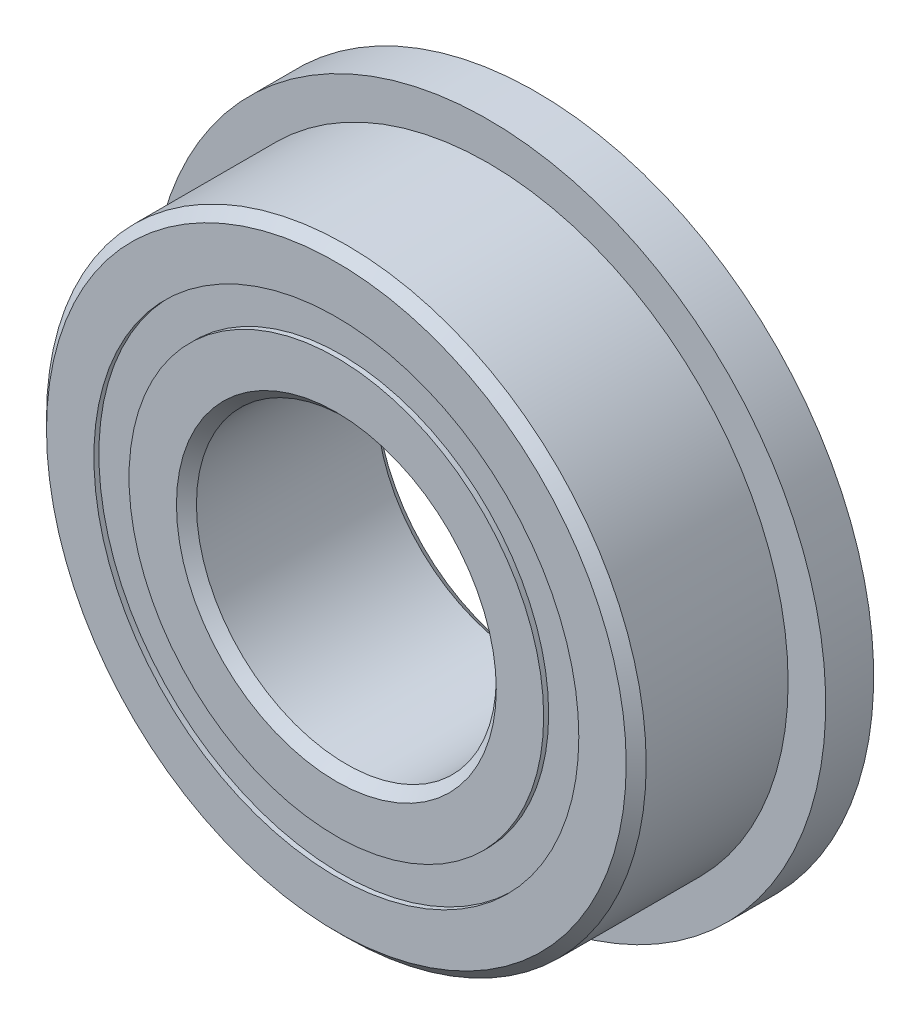
SolidWorks part; units mm, degrees
ref_plane "Front Plane" through (0, 0, 0) normal (0, 0, 1) x (1, 0, 0)
ref_plane "Top Plane" through (0, 0, 0) normal (0, 1, 0) x (1, 0, 0)
ref_plane "Right Plane" through (0, 0, 0) normal (1, 0, 0) x (0, 0, -1)
sketch "Sketch1" plane through (0, 0, 0) normal (1, 0, 0) x (0, 0, -1)
  line L0 (-1.5875, 0) -> (1.5875, 0) construction
  line L1 (0, 4.7625) -> (0, -4.7625) construction
  line L2 (1.5875, 4.7625) -> (-1.5875, 4.7625) construction
  line L9 (0, 4.7625) -> (0, 3.5719) construction
  line L10 (0, 3.5719) -> (0, 2.3813) construction
  point P14 (0, 2.3813)
  dimension "Width" = 3.175
  dimension "OD" = 9.525
  dimension "Shaft Dia" = 4.7625
sketch "Sketch2" plane through (0, 0, 0) normal (1, 0, 0) x (0, 0, -1)
  line L0 (1.9844, 0) -> (-1.9844, 0) construction
  line L1 (1.5875, 3.851) -> (0.8255, 3.851) construction
  line L2 (1.5875, 3.851) -> (1.5875, 5.3594) construction
  line L3 (1.5875, 5.3594) -> (0.8255, 5.3594) construction
  line L4 (0.8255, 3.851) -> (0.8255, 5.3594) construction
  dimension "Th" = 0.762
  dimension "Flange OD" = 10.7188
  dimension "D1" = 0.2791
sketch "Sketch" plane through (0, 0, 0) normal (1, 0, 0) x (0, 0, -1)
  line L0 (-1.5875, 0) -> (1.5875, 0) construction
  line L1 (0, 4.7625) -> (0, -4.7625) construction
  line L2 (1.4287, 4.7625) -> (-1.4287, 4.7625)
  line L3 (-1.4287, 4.7625) -> (-1.5875, 4.6038)
  line L4 (-1.5875, 4.6038) -> (-1.5875, 3.851)
  line L5 (-1.5875, 3.851) -> (-0.7056, 3.851)
  line L6 (1.5875, 3.851) -> (0.7056, 3.851)
  line L7 (1.5875, 4.6038) -> (1.5875, 3.851)
  line L8 (1.4287, 4.7625) -> (1.5875, 4.6038)
  line L9 (0, 4.7625) -> (0, 3.5719) construction
  line L10 (0, 3.5719) -> (0, 2.3813) construction
  arc A0 (-0.7056, 3.851) -> (0.7056, 3.851) centre (0, 3.5719) cw
  point P14 (0, 2.3813)
  dimension "D1" = 45
  dimension "D2" = 0.1588
  dimension "D3" = 1.4111
  dimension "D4" = 0.2791
revolve "Revolve1" add sketch "Sketch" angle 360 about L0
sketch "Sketch3" plane through (0, 0, 0) normal (1, 0, 0) x (0, 0, -1)
  line L0 (-1.5875, 3.2928) -> (-0.7056, 3.2928)
  line L1 (0, 4.7625) -> (0, -4.7625) construction
  line L2 (-1.5875, 4.6038) -> (-1.5875, 3.851) construction
  line L3 (-1.5875, 3.2928) -> (-1.5875, 2.54)
  line L4 (-1.4287, 4.7625) -> (-1.5875, 4.6038) construction
  line L5 (-1.5875, 2.54) -> (-1.4287, 2.3813)
  line L6 (-1.4287, 2.3813) -> (1.4287, 2.3813)
  line L7 (1.4287, 4.7625) -> (1.4287, -4.7625) construction
  line L8 (1.4287, 2.3813) -> (1.5875, 2.54)
  line L9 (1.5875, -4.6038) -> (1.5875, 4.6038) construction
  line L10 (1.5875, 2.54) -> (1.5875, 3.2928)
  line L11 (1.5875, 3.2928) -> (0.7056, 3.2928)
  line L13 (1.4287, 4.7625) -> (1.5875, 4.6038) construction
  arc A0 (0.7056, 3.851) -> (-0.7056, 3.851) centre (0, 3.5719) ccw construction
  arc A1 (0.7056, 3.2928) -> (-0.7056, 3.2928) centre (0, 3.5719) cw
revolve "Revolve3" add sketch "Sketch3" angle 360 about L0
sketch "Sketch4" plane through (0, 0, 0) normal (1, 0, 0) x (0, 0, -1)
  line L0 (-0.7588, 3.5719) -> (0.7588, 3.5719)
  arc A2 (-0.7588, 3.5719) -> (0.7588, 3.5719) centre (0, 3.5719) cw
  arc A3 (0.7056, 3.851) -> (-0.7056, 3.851) centre (0, 3.5719) ccw construction
revolve "Revolve4" add sketch "Sketch4" angle 360 about L0
ref_axis "Axis1" through (0, 0, -1.5875) along (0, 0, 1)
pattern_circular "CirPattern1" count 12 every 30 about axis through (0, 0, -1.5875) along (0, 0, 1) of bodies 104
sketch "Sketch5" plane through (0, 0, 0) normal (1, 0, 0) x (0, 0, -1)
  line L0 (-1.5875, 3.851) -> (-0.7056, 3.851) construction
  line L1 (-1.5081, 3.851) -> (-0.7588, 3.851)
  line L2 (-1.5081, 3.851) -> (-1.5081, 3.2928)
  line L3 (-1.5081, 3.2928) -> (-0.7588, 3.2928)
  line L4 (-0.7588, 3.851) -> (-0.7588, 3.2928)
  line L5 (-1.5875, 3.2928) -> (-0.7056, 3.2928) construction
  line L6 (1.5875, 3.851) -> (0.7056, 3.851) construction
  line L7 (1.5081, 3.851) -> (0.7588, 3.851)
  line L8 (1.5081, 3.851) -> (1.5081, 3.2928)
  line L9 (1.5081, 3.2928) -> (0.7588, 3.2928)
  line L10 (0.7588, 3.851) -> (0.7588, 3.2928)
  line L11 (1.5875, 3.2928) -> (0.7056, 3.2928) construction
  line L12 (-1.4287, 4.7625) -> (-1.5875, 4.6038) construction
  point P18 (-1.5081, 4.6831)
revolve "Revolve5" add sketch "Sketch5" angle 360 about L0
sketch "Sketch6" plane through (0, 0, 0) normal (1, 0, 0) x (0, 0, -1)
  line L0 (1.5875, 0) -> (-1.5875, 0) construction
  line L1 (1.5875, 3.851) -> (0.8255, 3.851)
  line L2 (1.5875, 3.851) -> (1.5875, 5.3594)
  line L3 (1.5875, 5.3594) -> (0.8255, 5.3594)
  line L4 (0.8255, 3.851) -> (0.8255, 5.3594)
  dimension "Th" = 0.762
  dimension "Flange OD" = 10.7188
revolve "Revolve6" add sketch "Sketch6" angle 360 about L0
sketch "Sketch7" plane through (0, 0, 0) normal (1, 0, 0) x (0, 0, -1)
  line L1 (1.5875, 4.7625) -> (-1.5875, 4.7625) construction
  line L2 (1.5875, 4.7625) -> (-1.5875, 4.7625) construction
  line L3 (1.5875, -4.7625) -> (-1.5875, -4.7625) construction
  line L4 (1.5875, -5.3594) -> (1.5875, 5.3594) construction
  line L5 (1.5875, 4.7625) -> (1.5875, 5.3594) construction
  line L6 (1.5875, 5.3594) -> (0.8255, 5.3594) construction
  dimension "D1" = 9.525
  dimension "D2" = 3.175
sketch "Sketch8" plane through (0, 0, 0) normal (0, 0, 1) x (1, 0, 0)
  circle A0 centre (0, 0) radius 2.3813 construction
  dimension "D1" = 4.7625
equation "\"D2@Sketch\" = \"Width@Sketch1\" * .05"
equation "\"D3@Sketch\" = \"Width@Sketch1\" / 2.25"
equation "\"D4@Sketch\"=(  (  ( \"OD@Sketch1\" - \"Width@Sketch1\" )  / 2 )  / 3.25 )  / 3.5"
equation "\"D2@CirPattern1\" = 360/\"Balls@CirPattern1\""
equation "\"D1@Sketch2\"=(  (  ( \"OD@Sketch1\" - \"Width@Sketch1\" )  / 2 )  / 3.25 )  / 3.5"
